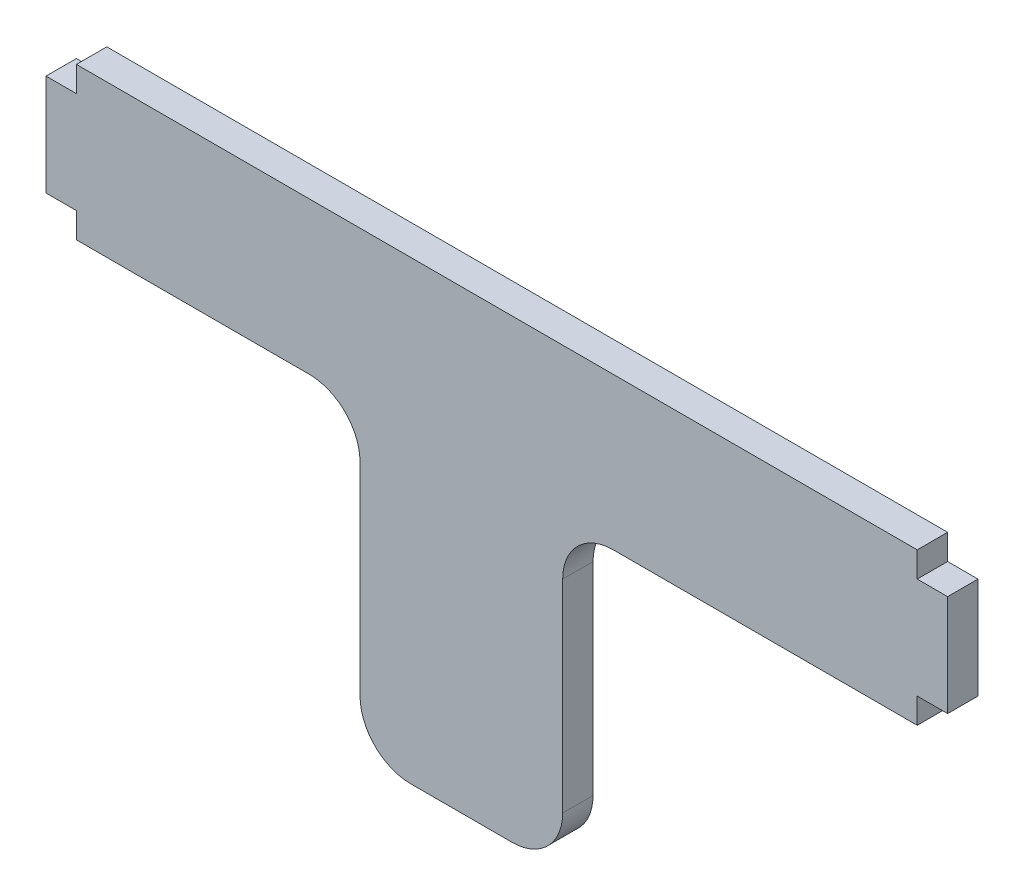
SolidWorks part; units mm, degrees
material "MDF"
ref_plane "Plano frontal" through (0, 0, 0) normal (0, 0, 1) x (1, 0, 0)
ref_plane "Plano superior" through (0, 0, 0) normal (0, 1, 0) x (1, 0, 0)
ref_plane "Plano direito" through (0, 0, 0) normal (1, 0, 0) x (0, 0, -1)
sketch "Esboço1" plane through (0, 0, 0) normal (0, 0, 1) x (1, 0, 0)
  line L0 (0, 0) -> (0, 7.5) construction
  line L1 (41.5, -7.5) -> (-41.5, -7.5)
  line L2 (41.5, -7.5) -> (41.5, 7.5)
  line L3 (41.5, 7.5) -> (-41.5, 7.5)
  line L4 (-41.5, -7.5) -> (-41.5, 7.5)
  line L5 (41.5, -7.5) -> (-41.5, 7.5) construction
  line L6 (41.5, 7.5) -> (-41.5, -7.5) construction
  line L7 (6.5, -37.5) -> (-13.5, -37.5)
  line L8 (6.5, -37.5) -> (6.5, -7.5)
  line L9 (6.5, -7.5) -> (-13.5, -7.5)
  line L10 (-13.5, -37.5) -> (-13.5, -7.5)
  line L11 (6.5, -37.5) -> (-13.5, -7.5) construction
  line L12 (6.5, -7.5) -> (-13.5, -37.5) construction
  line L13 (-44.5, -5) -> (-41.5, -5)
  line L14 (-44.5, -5) -> (-44.5, 5)
  line L15 (-44.5, 5) -> (-41.5, 5)
  line L16 (-41.5, -5) -> (-41.5, 5)
  line L17 (-44.5, -5) -> (-41.5, 5) construction
  line L18 (-44.5, 5) -> (-41.5, -5) construction
  line L19 (44.5, 5) -> (41.5, 5)
  line L20 (41.5, -5) -> (41.5, 5)
  line L21 (44.5, -5) -> (41.5, -5)
  line L22 (44.5, -5) -> (44.5, 5)
  point P0 (0, 0)
  point P6 (-3.5, -22.5)
  point P12 (-43, 0)
  dimension "D1" = 83
  dimension "D2" = 30
  dimension "D3" = 15
  dimension "D4" = 20
  dimension "D5" = 3
  dimension "D6" = 10
  dimension "D7" = 48
extrude "Ressalto-extrusão1" add sketch "Esboço1" along normal blind 3 contours L4 L1 L2 L3 | L10 L7 L8 L1 | L21 L22 L19 L2 | L15 L14 L13 L4 region at (0, 0, 0) region at (-3.5, -22.5, 0) region at (43, 0, 0) region at (-43, 0, 0)
fillet "Filete1" radius 5 4 edges at (6.5, -37.5, 1.5) (-13.5, -37.5, 1.5) (-13.5, -7.5, 1.5) (6.5, -7.5, 1.5)
